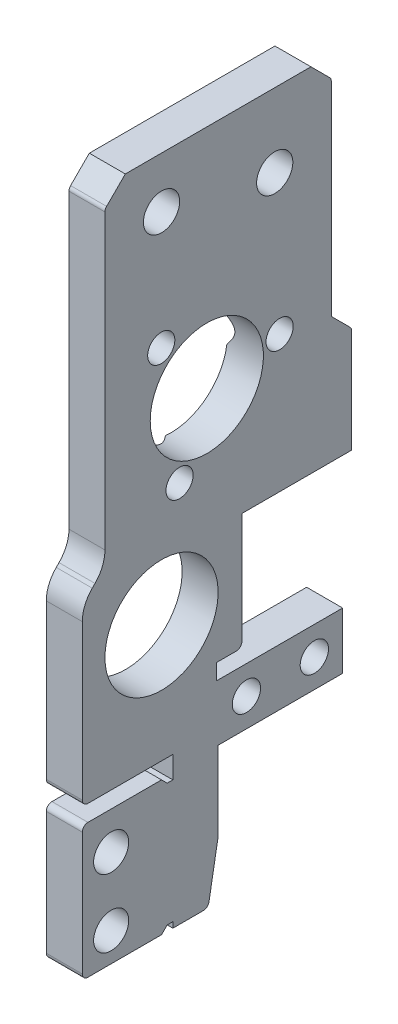
SolidWorks part; units mm, degrees
ref_plane "Front Plane" through (0, 0, 0) normal (0, 0, 1) x (1, 0, 0)
ref_plane "Top Plane" through (0, 0, 0) normal (0, 1, 0) x (1, 0, 0)
ref_plane "Right Plane" through (0, 0, 0) normal (1, 0, 0) x (0, 0, -1)
sketch "Sketch1" plane through (0, 0, 0) normal (1, 0, 0) x (0, 0, -1)
  line L2 (0, 0) -> (0, 11.85)
  line L3 (0, 28.7) -> (2, 30.7)
  line L4 (2, 30.7) -> (2, 59.81)
  line L5 (2, 59.81) -> (22, 59.81)
  line L7 (23.8, 28.68) -> (14.1, 28.68)
  line L8 (11.85, 18.4) -> (11.85, 17)
  line L9 (11.85, 17) -> (23, 17)
  line L10 (23, 17) -> (23, 12)
  line L11 (23, 12) -> (12, 12)
  line L12 (12, 12) -> (12, 0)
  line L13 (12, 0) -> (8, 0)
  line L14 (-8.9356, -4) -> (60.4069, -4) construction
  line L15 (7, 28.7) -> (0, 28.7) construction
  line L16 (2, 30.7) -> (2, 20.9492) construction
  line L17 (0, 11.85) -> (7, 11.85)
  line L18 (11.85, 18.4) -> (14.1, 18.4)
  line L19 (14.1, 18.4) -> (14.1, 28.68)
  line L23 (22, 59.81) -> (22, 39.81)
  line L26 (22, 39.81) -> (23.8, 39.81)
  line L27 (23.8, 39.81) -> (23.8, 28.68)
  line L30 (8, 11.35) -> (8, 13.3)
  line L31 (8, 13.3) -> (0, 13.3)
  line L32 (0, 13.3) -> (0, 28.7)
  line L33 (7, 11.85) -> (7.5, 11.35)
  line L34 (7.5, 11.35) -> (8, 11.35)
  line L35 (8, 0) -> (8, 0.5)
  line L36 (8, 0.5) -> (7.5, 0.5)
  line L37 (7.5, 0.5) -> (7, 0)
  line L38 (7, 0) -> (0, 0)
  circle A0 centre (7, 23.7) radius 5
  circle A1 centre (7, 55.31) radius 1.6
  circle A2 centre (17, 53.31) radius 1.6
  circle A3 centre (20.5, 14.5) radius 1.25
  circle A4 centre (14.5, 14.5) radius 1.25
  circle A5 centre (2.55, 2.55) radius 1.55
  circle A6 centre (2.55, 8.55) radius 1.55
  dimension "D11" = 10
  dimension "D13" = 3.2
  dimension "D17" = 5
  dimension "D21" = 2.5
  dimension "D29" = 6
  dimension "D28" = 3.1
  dimension "D30" = 2.55
  dimension "D3" = 31.13
  dimension "D4" = 5
  dimension "D5" = 11.68
  dimension "D6" = 11.15
  dimension "D7" = 10
  dimension "D8" = 4
  dimension "D9" = 2
  dimension "D10" = 2
  dimension "D12" = 36.11
  dimension "D14" = 6.5
  dimension "D15" = 4.5
  dimension "D16" = 5
  dimension "D18" = 6
  dimension "D19" = 2.5
  dimension "D20" = 2.5
  dimension "D22" = 1.4
  dimension "D23" = 2.25
  dimension "D24" = 20
  dimension "D25" = 11
  dimension "D26" = 1.8
  dimension "D27" = 20
  dimension "D31" = 2.55
  dimension "D32" = 11.85
  dimension "D33" = 7
  dimension "D34" = 0.5
  dimension "D35" = 0.5
  dimension "D36" = 1.45
  dimension "D37" = 0.5
  dimension "D38" = 59.81
extrude "Boss-Extrude1" add sketch "Sketch1" along normal blind 3.18
chamfer "Chamfer1" distance 5 angle 10 1 edges at (1.59, 0, -12) first distance on face at (1.59, 6, -12)
fillet "Fillet1" [suppressed] radius 1
sketch "Sketch3" plane through (0, 0, 0) normal (-1, 0, 0) x (0, 0, 1)
  line L1 (-17.4326, 40.7448) -> (-6.9749, 44.9147) construction
  line L2 (-6.9749, 44.9147) -> (-8.5925, 33.7732) construction
  line L3 (-8.5925, 33.7732) -> (-17.4326, 40.7448) construction
  line L4 (-2, 59.81) -> (-2, 30.7) construction
  circle A0 centre (-11, 39.8109) radius 5
  circle A2 centre (-11, 39.8109) radius 6.5 construction
  circle A3 centre (-6.9749, 44.9147) radius 1.2 construction
  circle A4 centre (-8.5925, 33.7732) radius 1.2 construction
  circle A5 centre (-17.4326, 40.7448) radius 1.2 construction
  circle A6 centre (-7, 23.7) radius 5 construction
  dimension "D1" = 10
  dimension "D3" = 16.6
  dimension "D4" = 13
  dimension "D5" = 2.4
  dimension "D2" = 9
hole_wizard "CSK for M2 Flat Head Machine Screw1" positions "Sketch6" profile "Sketch7" countersink size "M2" standard "ANSI Metric"
sketch "Sketch6" plane through (0, 0, 0) normal (-1, 0, 0) x (0, 0, 1)
  point P0 (-6.9749, 44.9147)
  point P3 (-17.4326, 40.7448)
  point P6 (-8.5925, 33.7732)
sketch "Sketch7" plane through (0, 44.9147, -6.9749) normal (0, 1, 0) x (0, 0, 1)
  line L0 (0, 0) -> (0, 4.23)
  line L1 (0, 4.23) -> (1.2, 3.509)
  line L2 (1.2, 3.509) -> (1.2, 1)
  line L3 (1.2, 1) -> (2.2, 0)
  line L5 (2.2, 0) -> (0, 0)
  line L6 (-1.2, 1) -> (-2.2, 0) construction
  line L10 (0, 4.23) -> (-1.2, 3.509) construction
  line L11 (0, -6.35) -> (0, 107.95) construction
  dimension "Hole Dia." = 2.4
  dimension "Hole Depth" = 4.23
  dimension "Near C'Sink Dia." = 4.4
  dimension "Near C'Sink Angle" = 90
  dimension "Drill Angle" = 118
extrude "Cut-Extrude4" cut sketch "Sketch3" against normal through all
sketch "Sketch8" plane through (3.18, 0, 0) normal (1, 0, 0) x (0, 0, -1)
  line L0 (2, 59.81) -> (2, 30.7) construction
  line L1 (11, 39.8109) -> (2, 39.8109) construction
  line L2 (2, 42.8109) -> (4.1261, 42.8109)
  line L3 (4.1261, 36.8109) -> (2, 36.8109)
  line L4 (2, 36.8109) -> (2, 42.8109)
  arc A0 (4.1261, 36.8109) -> (4.1261, 42.8109) centre (11, 39.8109) ccw
  circle A1 centre (7, 23.7) radius 5 construction
  point P11 (2, 39.8109)
  dimension "D1" = 16.6
  dimension "D2" = 15
  dimension "D3" = 9
  dimension "D4" = 6
extrude "Cut-Extrude5" [suppressed] cut sketch "Sketch8" against normal through all
fillet "Fillet2" radius 3 2 edges at (1.59, 30.7, -2) (1.59, 28.7, 0)
fillet "Chamfer2" radius 1.8 3 edges at (1.59, 59.81, -22) (1.59, 59.81, -2) (1.59, 39.81, -23.8) profile chamfer
fillet "Fillet4" radius 0.5 8 edges at (1.59, 58.01, -2) (1.59, 58.01, -22) (1.59, 18.4, -14.1) (1.59, 0, -11.1184) (1.59, 38.01, -23.8) (1.59, 13.3, 0) (1.59, 11.85, 0) (1.59, 0, 0)
